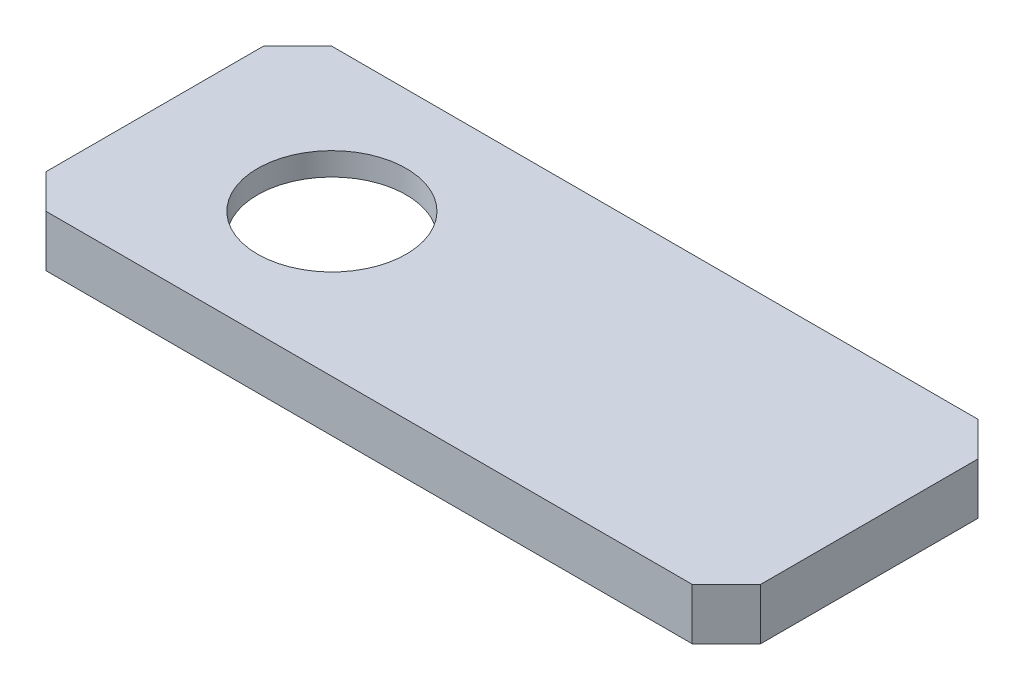
SolidWorks part; units mm, degrees
ref_plane "Спереди" through (0, 0, 0) normal (0, 0, 1) x (1, 0, 0)
ref_plane "Сверху" through (0, 0, 0) normal (0, 1, 0) x (1, 0, 0)
ref_plane "Справа" through (0, 0, 0) normal (1, 0, 0) x (0, 0, -1)
sketch "Эскиз1" plane through (0, 0, 0) normal (0, 1, 0) x (1, 0, 0)
  line L0 (25.8931, 8.2346) -> (-15.6069, 8.2346)
  line L1 (-15.0089, -13.7654) -> (26.4911, -13.7654)
  line L2 (-24.9069, -8.7654) -> (-15.0089, -13.7654)
  line L3 (35.5931, -12.2654) -> (35.5931, 6.7346)
  line L4 (35.5931, 6.7346) -> (32.5931, 9.7346)
  line L5 (32.5931, 9.7346) -> (-23.9069, 9.7346)
  line L6 (-23.9069, 9.7346) -> (-26.9069, 6.7346)
  line L7 (-26.9069, 6.7346) -> (-26.9069, -12.2654)
  line L8 (-26.9069, -12.2654) -> (-23.9069, -15.2654)
  line L9 (-23.9069, -15.2654) -> (32.5931, -15.2654)
  line L10 (32.5931, -15.2654) -> (35.5931, -12.2654)
  line L11 (-24.9069, 2.2346) -> (-24.9069, -8.7654)
  line L12 (-15.6069, 8.2346) -> (-24.9069, 2.2346)
  line L14 (26.4911, -13.7654) -> (33.5931, -10.2654)
  line L15 (33.5931, -10.2654) -> (33.5931, 4.7346)
  line L16 (33.5931, 4.7346) -> (32.5963, 5.1877)
  line L17 (30.1447, 6.3021) -> (25.8931, 8.2346)
  circle A0 centre (-22.9069, -11.7654) radius 1.45
  arc A1 (32.5963, 5.1877) -> (30.1447, 6.3021) centre (31.5931, 6.2346) ccw
extrude "Бобышка-Вытянуть1" add sketch "Эскиз1" along normal blind 2.5
sketch "Эскиз2" plane through (0, 2.5, 0) normal (0, 1, 0) x (1, 0, 0)
  line L8 (32.5931, -15.2654) -> (35.5931, -12.2654)
  line L9 (35.5931, -12.2654) -> (35.5931, 6.7346)
  line L10 (35.5931, 6.7346) -> (32.5931, 9.7346)
  line L11 (32.5931, 9.7346) -> (-23.9069, 9.7346)
  line L12 (-23.9069, 9.7346) -> (-26.9069, 6.7346)
  line L13 (-26.9069, 6.7346) -> (-26.9069, -12.2654)
  line L14 (-26.9069, -12.2654) -> (-23.9069, -15.2654)
  line L15 (-23.9069, -15.2654) -> (32.5931, -15.2654)
  line L16 (32.5931, -15.2654) -> (35.5931, -12.2654)
  line L17 (35.5931, -12.2654) -> (35.5931, 6.7346)
  line L18 (35.5931, 6.7346) -> (32.5931, 9.7346)
  line L19 (32.5931, 9.7346) -> (-23.9069, 9.7346)
  line L20 (-23.9069, 9.7346) -> (-26.9069, 6.7346)
  line L21 (-26.9069, 6.7346) -> (-26.9069, -12.2654)
  line L22 (-26.9069, -12.2654) -> (-23.9069, -15.2654)
  line L23 (-23.9069, -15.2654) -> (32.5931, -15.2654)
  dimension "D1" = 0
extrude "Бобышка-Вытянуть2" add sketch "Эскиз2" along normal blind 2
sketch "Эскиз3" plane through (0, 4.5, 0) normal (0, 1, 0) x (1, 0, 0)
  line L0 (32.5931, 9.7346) -> (-23.9069, 9.7346) construction
  line L1 (-26.9069, 6.7346) -> (-26.9069, -12.2654) construction
  circle A0 centre (-11.4069, -2.7654) radius 6.5
  dimension "D3" = 13
  dimension "D1" = 12.5
  dimension "D2" = 15.5
extrude "Вырез-Вытянуть1" cut sketch "Эскиз3" against normal through all
sketch "Эскиз4" plane through (0, 2.5, 0) normal (0, -1, 0) x (1, 0, 0)
  circle A0 centre (31.5931, -6.2346) radius 1.45
  circle A1 centre (-22.9069, 11.7654) radius 1.45
  circle A2 centre (-22.9069, 11.7654) radius 1.45
  arc A3 (30.1447, -6.3021) -> (32.5963, -5.1877) centre (31.5931, -6.2346) ccw construction
  dimension "D1" = 0
extrude "Вырез-Вытянуть2" cut sketch "Эскиз4" against normal blind 1
sketch "Эскиз6" plane through (0, 2.5, 0) normal (0, -1, 0) x (1, 0, 0)
  line L0 (4.3431, -984.7346) -> (4.3431, 49015.2654) construction
  line L1 (-23.9069, 15.2654) -> (32.5931, 15.2654) construction
  line L2 (-1026.9069, 2.7654) -> (48973.0931, 2.7654) construction
  line L3 (-26.9069, -6.7346) -> (-26.9069, 12.2654) construction
  circle A0 centre (4.3431, 2.7654) radius 5
  point P5 (4.3431, 15.2654)
  point P10 (-26.9069, 2.7654)
  dimension "D1" = 10
extrude "Вырез-Вытянуть4" cut sketch "Эскиз6" against normal blind 1
